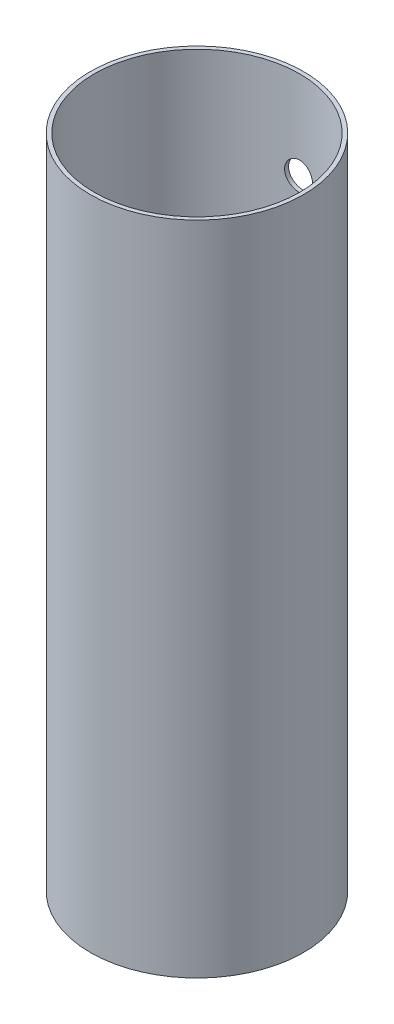
SolidWorks part; units mm, degrees
ref_plane "Front Plane" through (0, 0, 0) normal (0, 0, 1) x (1, 0, 0)
ref_plane "Top Plane" through (0, 0, 0) normal (0, 1, 0) x (1, 0, 0)
ref_plane "Right Plane" through (0, 0, 0) normal (1, 0, 0) x (0, 0, -1)
sketch "Sketch1" plane through (0, 0, 0) normal (0, 1, 0) x (1, 0, 0)
  circle A0 centre (0, 0) radius 49.5173
  circle A1 centre (0, 0) radius 47.6885
  dimension "D1" = 99.0346
  dimension "D2" = 95.377
extrude "Boss-Extrude1" add sketch "Sketch1" along normal blind 304.8
sketch "Sketch6" plane through (0, 0, 0) normal (1, 0, 0) x (0, 0, -1)
  line L0 (47.6885, 304.8) -> (-47.6885, 304.8) construction
  line L1 (-49.5173, 0) -> (49.5173, 0) construction
  point P0 (0, 263.525)
  point P1 (0, 41.402)
  dimension "D1" = 41.275
  dimension "D2" = 41.402
hole_wizard "1/2 Clearance Hole8" positions "Sketch28" profile "Sketch29" hole size "1/2" standard "ANSI Inch" end condition through all
sketch "Sketch28" plane through (0, 0, 0) normal (0, 0, 1) x (1, 0, 0)
  point P0 (0, 263.525)
  point P3 (0, 41.402)
sketch "Sketch29" plane through (0, 263.525, 0) normal (1, 0, 0) x (0, -1, 0)
  line L0 (0, 0) -> (0, 49.5173)
  line L1 (0, 49.5173) -> (6.5481, 49.5173)
  line L2 (6.5481, 49.5173) -> (6.5481, 0)
  line L5 (6.5481, 0) -> (0, 0)
  line L11 (0, -6.35) -> (0, 107.95) construction
  dimension "Thru Hole Dia." = 13.0962
  dimension "Thru Hole Depth" = 49.5173
equation "\"Coupler_OD\" = 3.899in"
equation "\"Coupler_ID\" = 3.755in"
equation "\"Mid_Coupler_Length\" = 12in"
equation "\"D1@Sketch1\"=\"Coupler_OD\""
equation "\"D2@Sketch1\"=\"Coupler_ID\""
equation "\"D1@Boss-Extrude1\"=\"Mid_Coupler_Length\""
